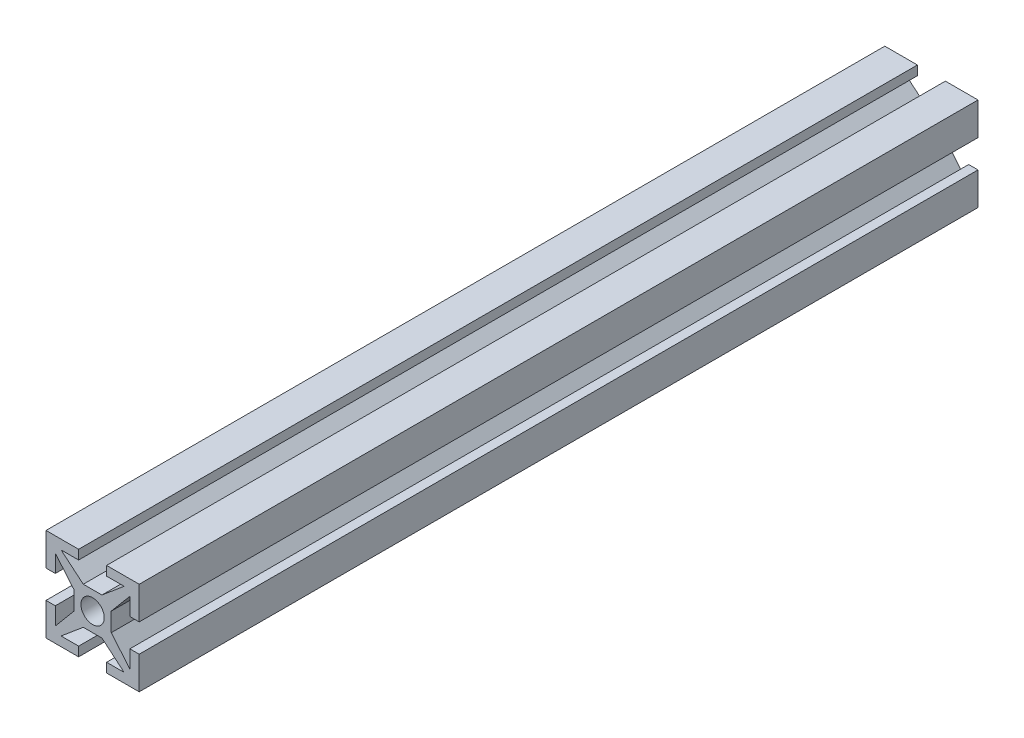
SolidWorks part; units mm, degrees
ref_plane "Front Plane" through (0, 0, 0) normal (0, 0, 1) x (1, 0, 0)
ref_plane "Top Plane" through (0, 0, 0) normal (0, 1, 0) x (1, 0, 0)
ref_plane "Right Plane" through (0, 0, 0) normal (1, 0, 0) x (0, 0, -1)
sketch "Esquisse2" plane through (0, 0, 0) normal (0, 0, 1) x (1, 0, 0)
  line L0 (-1, -2) -> (1, -2)
  line L1 (1, -2) -> (3.3835, -4)
  line L2 (3.3835, -4) -> (1.5, -4)
  line L3 (1.5, -4) -> (1.5, -5)
  line L4 (1.5, -5) -> (5, -5)
  line L5 (-1, -2) -> (-3.3835, -4)
  line L6 (-3.3835, -4) -> (-1.5, -4)
  line L7 (-1.5, -4) -> (-1.5, -5)
  line L8 (-1.5, -5) -> (-5, -5)
  line L9 (-5, -5) -> (-5, -1.5)
  line L10 (-5, -1.5) -> (-4, -1.5)
  line L11 (-4, -1.5) -> (-4, -3.3835)
  line L12 (-4, -3.3835) -> (-2, -1)
  line L13 (-2, -1) -> (-2, 1)
  line L14 (-2, 1) -> (-4, 3.3835)
  line L15 (-4, 3.3835) -> (-4, 1.5)
  line L16 (-4, 1.5) -> (-5, 1.5)
  line L17 (-5, 1.5) -> (-5, 5)
  line L18 (-5, 5) -> (-1.5, 5)
  line L19 (-1.5, 5) -> (-1.5, 4)
  line L20 (-1.5, 4) -> (-3.3835, 4)
  line L21 (-3.3835, 4) -> (-1, 2)
  line L22 (-1, 2) -> (1, 2)
  line L23 (1, 2) -> (3.3835, 4)
  line L24 (3.3835, 4) -> (1.5, 4)
  line L25 (1.5, 4) -> (1.5, 5)
  line L26 (1.5, 5) -> (5, 5)
  line L27 (5, 5) -> (5, 1.5)
  line L28 (5, 1.5) -> (4, 1.5)
  line L29 (4, 1.5) -> (4, 3.3835)
  line L30 (4, 3.3835) -> (2, 1)
  line L31 (2, -1) -> (2, 1)
  line L32 (2, -1) -> (4, -3.3835)
  line L33 (4, -3.3835) -> (4, -1.5)
  line L34 (4, -1.5) -> (5, -1.5)
  line L35 (5, -1.5) -> (5, -5)
  circle A0 centre (0, 0) radius 1.25
  point P4 (0, -2)
  point P34 (0, 2)
  point P40 (2, 0)
  dimension "D4" = 2.5
  dimension "D1" = 2
  dimension "D2" = 3.5
  dimension "D3" = 1
  dimension "D5" = 10
  dimension "D6" = 10
  dimension "D7" = 140
  dimension "D8" = 4
  dimension "D9" = 4
  dimension "D10" = 3.5
  dimension "D11" = 3
extrude "Main Extrusion" add sketch "Esquisse2" along normal blind 90
